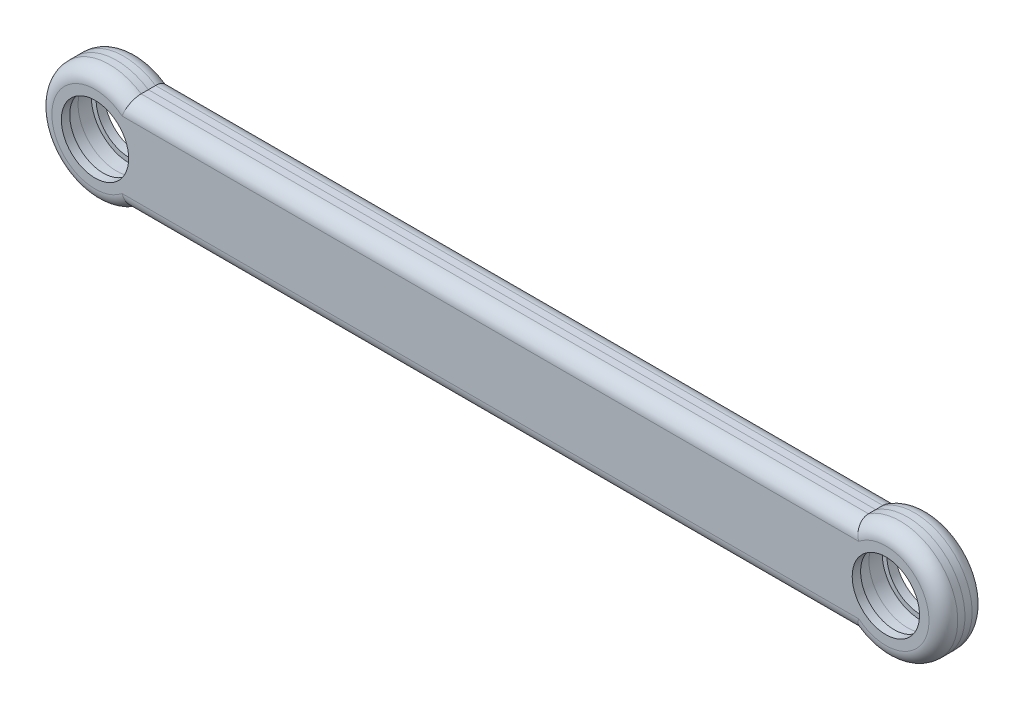
SolidWorks part; units mm, degrees
ref_plane "Front Plane" through (0, 0, 0) normal (0, 0, 1) x (1, 0, 0)
ref_plane "Top Plane" through (0, 0, 0) normal (0, 1, 0) x (1, 0, 0)
ref_plane "Right Plane" through (0, 0, 0) normal (1, 0, 0) x (0, 0, -1)
sketch "Sketch6" plane through (0, 0, 0) normal (0, 0, 1) x (1, 0, 0)
  line L0 (6.6332, -10) -> (158.3668, -10)
  line L2 (6.6332, 10) -> (158.3668, 10)
  line L3 (-58.5211, 0) -> (213.089, 0) construction
  line L6 (82.5, 22.0784) -> (82.5, -23.3181) construction
  circle A2 centre (165, 0) radius 12 construction
  circle A3 centre (0, 0) radius 8.025
  circle A4 centre (0, 0) radius 12 construction
  circle A8 centre (0, 0) radius 7.025
  arc A14 (6.6332, 10) -> (6.6332, -10) centre (0, 0) ccw
  circle A16 centre (165, 0) radius 7.025
  circle A17 centre (165, 0) radius 8.025
  arc A18 (158.3668, 10) -> (158.3668, -10) centre (165, 0) cw
  dimension "D2" = 1
  dimension "D3" = 165
  dimension "D4" = 16.05
  dimension "D5" = 24
  dimension "D8" = 20
extrude "Boss-Extrude1" add sketch "Sketch6" along normal mid plane 9 contours L2 A18 L0 A14
extrude "Cut-Extrude1" cut sketch "Sketch6<23>" along normal mid plane 5.5 contours A3 | A17
sketch "Sketch6<23>" plane through (0, 0, 0) normal (0, 0, 1) x (1, 0, 0) same geometry as "Sketch6"
extrude "Cut-Extrude2" cut sketch "Sketch6<24>" along normal through all both and the other way through all contours A8 | A16
sketch "Sketch6<24>" plane through (0, 0, 0) normal (0, 0, 1) x (1, 0, 0) same geometry as "Sketch6"
fillet "Fillet1" radius 3 8 edges at (-12, 0, 4.5) (177, 0, 4.5) (82.5, -10, 4.5) (82.5, 10, 4.5) (82.5, -10, -4.5) (82.5, 10, -4.5) (177, 0, -4.5) (-12, 0, -4.5)
split "Split1" trim tools "Front Plane" bodies to split 132 resulting bodies 146 147
